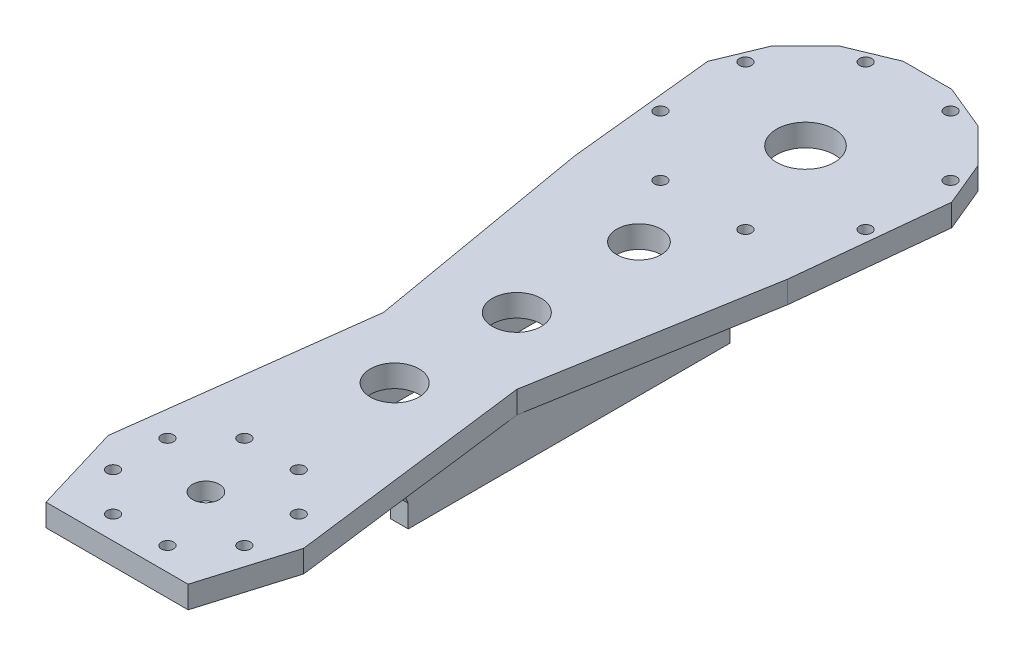
SolidWorks part; units mm, degrees
ref_plane "Front Plane" through (0, 0, 0) normal (0, 0, 1) x (1, 0, 0)
ref_plane "Top Plane" through (0, 0, 0) normal (0, 1, 0) x (1, 0, 0)
ref_plane "Right Plane" through (0, 0, 0) normal (1, 0, 0) x (0, 0, -1)
ref_plane "PL_Thigh_Plate_base" through (0, 36, 0) normal (0, 1, 0) x (1, 0, 0)
sketch "SK_Thigh_Plate" plane through (0, 36, 0) normal (0, 1, 0) x (1, 0, 0)
  line L0 (-32, -40) -> (32, -40)
  line L1 (32, -40) -> (44, 0)
  line L2 (44, 0) -> (30, 110)
  line L3 (30, 110) -> (48, 214)
  line L4 (48, 214) -> (54.924, 280.9251)
  line L5 (54.924, 280.9251) -> (46.5623, 301.1119)
  line L6 (46.5623, 301.1119) -> (31.1119, 316.5623)
  line L7 (31.1119, 316.5623) -> (10.9251, 324.924)
  line L8 (10.9251, 324.924) -> (-10.9251, 324.924)
  line L9 (-10.9251, 324.924) -> (-31.1119, 316.5623)
  line L10 (-31.1119, 316.5623) -> (-46.5623, 301.1119)
  line L11 (-46.5623, 301.1119) -> (-54.924, 280.9251)
  line L12 (-54.924, 280.9251) -> (-48, 214)
  line L13 (-48, 214) -> (-30, 110)
  line L14 (-30, 110) -> (-44, 0)
  line L15 (-44, 0) -> (-32, -40)
  circle A0 centre (29.5641, 12.2459) radius 2.75
  circle A1 centre (12.2459, 29.5641) radius 2.75
  circle A2 centre (-12.2459, 29.5641) radius 2.75
  circle A3 centre (-29.5641, 12.2459) radius 2.75
  circle A4 centre (-29.5641, -12.2459) radius 2.75
  circle A5 centre (-12.2459, -29.5641) radius 2.75
  circle A6 centre (12.2459, -29.5641) radius 2.75
  circle A7 centre (29.5641, -12.2459) radius 2.75
  circle A8 centre (46.194, 289.1342) radius 2.75
  circle A9 centre (19.1342, 316.194) radius 2.75
  circle A10 centre (-19.1342, 316.194) radius 2.75
  circle A11 centre (-46.194, 289.1342) radius 2.75
  circle A12 centre (-46.194, 250.8658) radius 2.75
  circle A13 centre (-19.1342, 223.806) radius 2.75
  circle A14 centre (19.1342, 223.806) radius 2.75
  circle A15 centre (46.194, 250.8658) radius 2.75
  circle A16 centre (0, 0) radius 6
  circle A17 centre (0, 270) radius 13
  circle A18 centre (0, 85) radius 11
  circle A19 centre (0, 140) radius 11
  circle A20 centre (0, 195) radius 10
  dimension "D31_SK_Thigh_Plate" = 5.5
  dimension "D34_SK_Thigh_Plate" = 5.5
  dimension "D37_SK_Thigh_Plate" = 5.5
  dimension "D40_SK_Thigh_Plate" = 5.5
  dimension "D43_SK_Thigh_Plate" = 5.5
  dimension "D46_SK_Thigh_Plate" = 5.5
  dimension "D49_SK_Thigh_Plate" = 5.5
  dimension "D52_SK_Thigh_Plate" = 5.5
  dimension "D55_SK_Thigh_Plate" = 5.5
  dimension "D58_SK_Thigh_Plate" = 5.5
  dimension "D61_SK_Thigh_Plate" = 5.5
  dimension "D64_SK_Thigh_Plate" = 5.5
  dimension "D67_SK_Thigh_Plate" = 5.5
  dimension "D70_SK_Thigh_Plate" = 5.5
  dimension "D73_SK_Thigh_Plate" = 5.5
  dimension "D76_SK_Thigh_Plate" = 5.5
  dimension "D79_SK_Thigh_Plate" = 12
  dimension "D80_SK_Thigh_Plate" = 26
  dimension "D82_SK_Thigh_Plate" = 22
  dimension "D84_SK_Thigh_Plate" = 22
  dimension "D86_SK_Thigh_Plate" = 20
  dimension "P1" = 32
  dimension "P2" = 40
  dimension "P3" = 32
  dimension "P4" = 40
  dimension "P5" = 44
  dimension "P6" = 30
  dimension "P7" = 110
  dimension "P8" = 48
  dimension "P9" = 214
  dimension "P10" = 54.924
  dimension "P11" = 280.9251
  dimension "P12" = 46.5623
  dimension "P13" = 301.1119
  dimension "P14" = 31.1119
  dimension "P15" = 316.5623
  dimension "P16" = 10.9251
  dimension "P17" = 324.924
  dimension "P18" = 10.9251
  dimension "P19" = 324.924
  dimension "P20" = 31.1119
  dimension "P21" = 316.5623
  dimension "P22" = 46.5623
  dimension "P23" = 301.1119
  dimension "P24" = 54.924
  dimension "P25" = 280.9251
  dimension "P26" = 48
  dimension "P27" = 214
  dimension "P28" = 30
  dimension "P29" = 110
  dimension "P30" = 44
  dimension "P32" = 29.5641
  dimension "P33" = 12.2459
  dimension "P35" = 12.2459
  dimension "P36" = 29.5641
  dimension "P38" = 12.2459
  dimension "P39" = 29.5641
  dimension "P41" = 29.5641
  dimension "P42" = 12.2459
  dimension "P44" = 29.5641
  dimension "P45" = 12.2459
  dimension "P47" = 12.2459
  dimension "P48" = 29.5641
  dimension "P50" = 12.2459
  dimension "P51" = 29.5641
  dimension "P53" = 29.5641
  dimension "P54" = 12.2459
  dimension "P56" = 46.194
  dimension "P57" = 289.1342
  dimension "P59" = 19.1342
  dimension "P60" = 316.194
  dimension "P62" = 19.1342
  dimension "P63" = 316.194
  dimension "P65" = 46.194
  dimension "P66" = 289.1342
  dimension "P68" = 46.194
  dimension "P69" = 250.8658
  dimension "P71" = 19.1342
  dimension "P72" = 223.806
  dimension "P74" = 19.1342
  dimension "P75" = 223.806
  dimension "P77" = 46.194
  dimension "P78" = 250.8658
  dimension "P81" = 270
  dimension "P83" = 85
  dimension "P85" = 140
  dimension "P87" = 195
extrude "Thigh_Plate" add sketch "SK_Thigh_Plate" along normal blind 10
ref_plane "PL_Pitch_Pilot_Recess_base" through (0, 36, 0) normal (0, 1, 0) x (1, 0, 0)
sketch "SK_Pitch_Pilot_Recess" plane through (0, 36, 0) normal (0, 1, 0) x (1, 0, 0)
  circle A0 centre (0, 0) radius 25.15
  dimension "D1_SK_Pitch_Pilot_Recess" = 50.3
extrude "Pitch_Pilot_Recess" cut sketch "SK_Pitch_Pilot_Recess" along normal blind 2.2
ref_plane "PL_Front_Flange_base" through (22, 0, 0) normal (1, 0, 0) x (0, 0, -1)
sketch "SK_Front_Flange" plane through (22, 0, 0) normal (1, 0, 0) x (0, 0, -1)
  line L0 (35.5977, 31) -> (35.5977, 36)
  line L1 (35.5977, 36) -> (206, 36)
  line L2 (206, 36) -> (206, 16)
  line L3 (206, 16) -> (61.0999, 16)
  line L4 (61.0999, 16) -> (61.0999, 26)
  line L5 (61.0999, 26) -> (59.0999, 31)
  line L6 (59.0999, 31) -> (35.5977, 31)
  dimension "P1" = 35.5977
  dimension "P2" = 31
  dimension "P3" = 35.5977
  dimension "P4" = 36
  dimension "P5" = 206
  dimension "P6" = 36
  dimension "P7" = 206
  dimension "P8" = 16
  dimension "P9" = 61.0999
  dimension "P10" = 16
  dimension "P11" = 61.0999
  dimension "P12" = 26
  dimension "P13" = 59.0999
  dimension "P14" = 31
extrude "Front_Flange" add sketch "SK_Front_Flange" along normal blind 8
ref_plane "PL_Back_Flange_base" through (-30, 0, 0) normal (1, 0, 0) x (0, 0, -1)
sketch "SK_Back_Flange" plane through (-30, 0, 0) normal (1, 0, 0) x (0, 0, -1)
  line L0 (35.5977, 31) -> (35.5977, 36)
  line L1 (35.5977, 36) -> (206, 36)
  line L2 (206, 36) -> (206, 16)
  line L3 (206, 16) -> (61.0999, 16)
  line L4 (61.0999, 16) -> (61.0999, 26)
  line L5 (61.0999, 26) -> (59.0999, 31)
  line L6 (59.0999, 31) -> (35.5977, 31)
  dimension "P1" = 35.5977
  dimension "P2" = 31
  dimension "P3" = 35.5977
  dimension "P4" = 36
  dimension "P5" = 206
  dimension "P6" = 36
  dimension "P7" = 206
  dimension "P8" = 16
  dimension "P9" = 61.0999
  dimension "P10" = 16
  dimension "P11" = 61.0999
  dimension "P12" = 26
  dimension "P13" = 59.0999
  dimension "P14" = 31
extrude "Back_Flange" add sketch "SK_Back_Flange" along normal blind 8
ref_axis "AX_PitchY" through (0, 47.5, 0) along (0, -1, 0)
ref_plane "PL_PitchRef" through (0, 0, 0) normal (-0.6428, 0, 0.766) x (0, -1, 0)
equation "\"Thigh_length\" = 270"
equation "\"Thigh_plate_t\" = 10"
equation "\"Flange_end_z\" = -206"
equation "\"Flange_deep_start_z\" = -61.0999"
equation "\"Flange_shallow_start_z\" = -35.5977"
